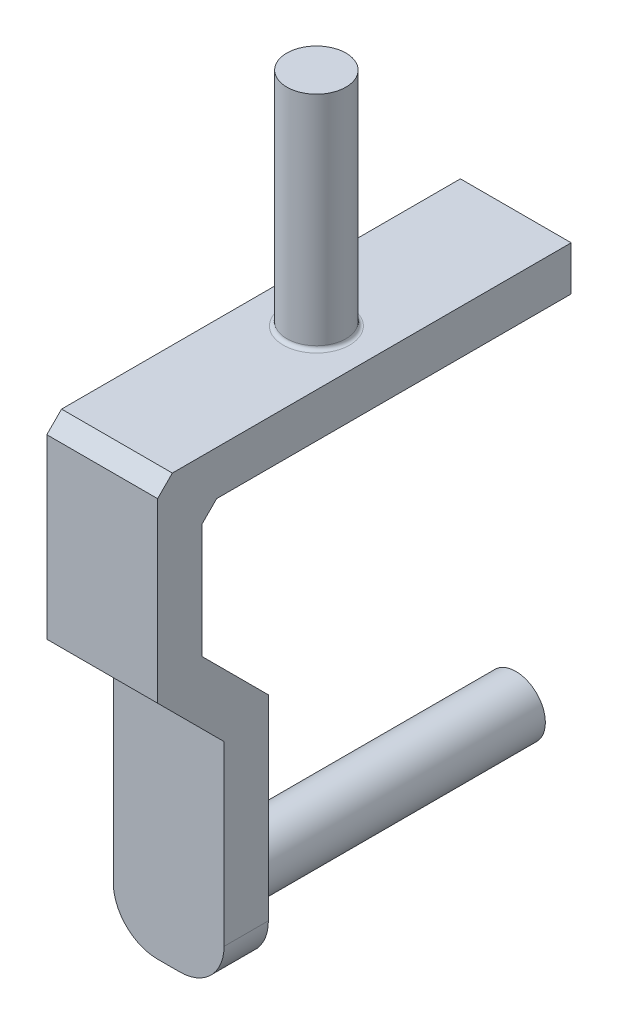
SolidWorks part; units mm, degrees
ref_plane "Alzado" through (0, 0, 0) normal (0, 0, 1) x (1, 0, 0)
ref_plane "Planta" through (0, 0, 0) normal (0, 1, 0) x (1, 0, 0)
ref_plane "Vista lateral" through (0, 0, 0) normal (1, 0, 0) x (0, 0, -1)
sketch "Croquis1" plane through (0, 0, 0) normal (0, 0, 1) x (1, 0, 0)
  line L0 (7.5, 32.5) -> (-7.5, -32.5) construction
  line L1 (-7.5, 32.5) -> (7.5, 32.5)
  line L2 (-7.5, 32.5) -> (-7.5, -32.5)
  line L3 (-7.5, -32.5) -> (7.5, -32.5)
  line L4 (7.5, 32.5) -> (7.5, -32.5)
  dimension "D1" = 65
  dimension "D2" = 15
extrude "Extruir1" add sketch "Croquis1" along normal blind 6
sketch "Croquis2" plane through (0, 0, 0) normal (0, 0, -1) x (-1, 0, 0)
  line L0 (-7.5, -32.5) -> (-7.5, 32.5) construction
  line L1 (7.5, 32.5) -> (-7.5, 32.5)
  line L2 (7.5, 32.5) -> (7.5, 26.5)
  line L3 (7.5, 26.5) -> (-7.5, 26.5)
  line L4 (-7.5, 32.5) -> (-7.5, 26.5)
  dimension "D1" = 6
extrude "Extruir2" add sketch "Croquis2" along normal blind 50
chamfer "Chaflán1" distance 2 angle 45 2 edges at (0, 32.5, 6)
sketch "Croquis3" plane through (0, 0, 0) normal (0, 0, -1) x (-1, 0, 0)
  line L0 (7.5, -32.5) -> (-7.5, -32.5) construction
  circle A0 centre (0, -25.5) radius 4
  dimension "D1" = 8
  dimension "D2" = 7
extrude "Extruir3" add sketch "Croquis3" along normal blind 50
chamfer "Chaflán2" distance 3 angle 45 1 edges at (4, -25.5, 0)
fillet "Redondeo1" radius 6 2 edges at (-7.5, -32.5, 3) (7.5, -32.5, 3)
sketch "Croquis4" plane through (0, 32.5, 0) normal (0, 1, 0) x (1, 0, 0)
  line L0 (7.5, -4) -> (-7.5, 50) construction
  circle A0 centre (0, 23) radius 4
  dimension "D1" = 8
extrude "Extruir4" add sketch "Croquis4" along normal blind 30
fillet "Redondeo2" radius 0.5 1 edges at (0, 32.5, -27)
sketch "Croquis6" plane through (0, 0, 6) normal (0, 0, 1) x (1, 0, 0)
  line L0 (7.5, 0) -> (-7.5, 0)
  line L4 (-7.5, 30.5) -> (-7.5, -26.5)
  line L5 (-1.5, -32.5) -> (1.5, -32.5)
  line L6 (7.5, -26.5) -> (7.5, 30.5)
  line L7 (7.5, 30.5) -> (-7.5, 30.5)
  line L8 (-7.5, 0) -> (-7.5, -26.5)
  line L9 (-1.5, -32.5) -> (1.5, -32.5)
  line L10 (7.5, -26.5) -> (7.5, 0)
  arc A2 (-7.5, -26.5) -> (-1.5, -32.5) centre (-1.5, -26.5) ccw
  arc A3 (1.5, -32.5) -> (7.5, -26.5) centre (1.5, -26.5) ccw
  arc A4 (-7.5, -26.5) -> (-1.5, -32.5) centre (-1.5, -26.5) ccw
  arc A5 (1.5, -32.5) -> (7.5, -26.5) centre (1.5, -26.5) ccw
  dimension "D1" = 0
extrude "Extruir5" add sketch "Croquis6" against normal blind 15
chamfer "Chaflán3" distance 9 angle 45 1 edges at (0, 0, 0)
sketch "Croquis7" plane through (7.5, 0, 0) normal (1, 0, 0) x (0, 0, -1)
  line L0 (-6, 6.5147) -> (3, -2.4853)
  line L1 (-6, -26.5) -> (-6, 30.5) construction
  line L2 (3, -2.4853) -> (3, -32.5)
  line L3 (9, -32.5) -> (-6, -32.5) construction
  line L4 (3, -32.5) -> (-11.9015, -39.5808)
  line L5 (-11.9015, -39.5808) -> (-6, 6.5147)
  line L7 (9, 0) -> (0, 9) construction
  line L8 (9, -26.5) -> (9, 0) construction
  dimension "D1" = 6
  dimension "D2" = 6
extrude "Extruir6" cut sketch "Croquis7" against normal blind 15
chamfer "Chaflán4" distance 3 angle 45 1 edges at (4, -25.5, -9)
